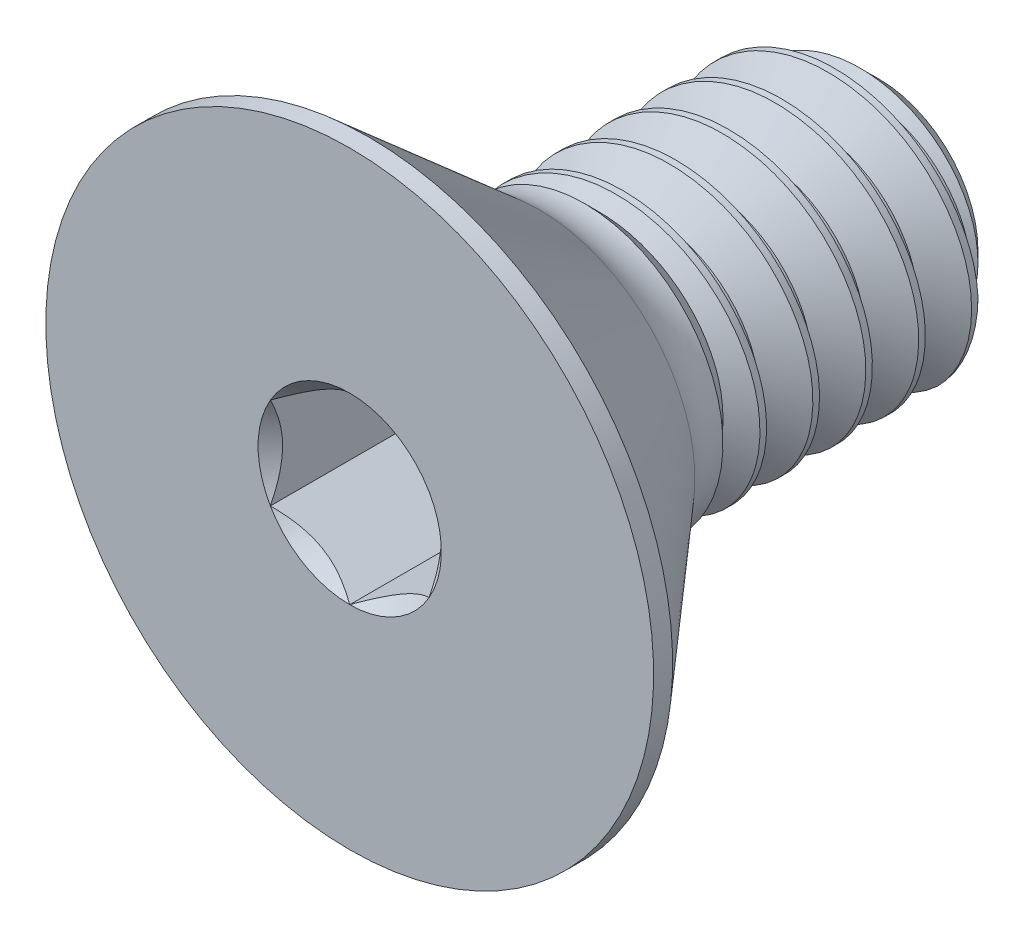
SolidWorks part; units mm, degrees
ref_plane "Front" through (0, 0, 0) normal (0, 0, 1) x (1, 0, 0)
ref_plane "Top" through (0, 0, 0) normal (0, 1, 0) x (1, 0, 0)
ref_plane "Right" through (0, 0, 0) normal (1, 0, 0) x (0, 0, -1)
sketch "Sketch1" plane through (0, 0, 0) normal (1, 0, 0) x (0, 0, -1)
  line L0 (0, 4.5593) -> (0.2845, 4.5593) construction
  line L1 (0.2845, 4.5593) -> (2.8448, 2.3336) construction
  line L2 (0, 2.0828) -> (7.9375, 2.0828)
  line L3 (7.9375, 2.0828) -> (7.9375, 0)
  line L4 (7.9375, 0) -> (0, 0)
  line L5 (0, 0) -> (0, 4.5593) construction
  line L6 (0, 4.5593) -> (0, -4.5593) construction
  line L7 (7.9375, 2.0828) -> (7.9375, -2.0828) construction
  line L8 (0, -4.5593) -> (0.2845, -4.5593) construction
  line L9 (0.2845, -4.5593) -> (2.8448, -2.3336) construction
  line L11 (0, 2.0828) -> (0, 0)
  line L12 (3.5157, 2.0828) -> (3.5157, 0) construction
  arc A1 (2.8448, 2.3336) -> (3.5157, 2.0828) centre (3.5157, 3.1055) ccw construction
  dimension "D1" = 0.2845
  dimension "Head Ht" = 2.8448
  dimension "Head Dia" = 9.1186
  dimension "Dia" = 4.1656
  dimension "Lg" = 7.9375
  dimension "Head Angle" = 82
revolve "Revolve1" add sketch "Sketch1" angle 360 about L4
sketch "Sketch3" plane through (0, 0, -7.9375) normal (0, 0, -1) x (-1, 0, 0)
  circle A0 centre (0, 0) radius 2.0828
curve "Helix/Spiral1" pitch 0.7937 height 7.9375 radius 2.0828 centre (0, 0, -7.9375) axis (0, 0, 1) start towards (0, 1, 0)
sketch "Sketch2" plane through (0, 0, 0) normal (1, 0, 0) x (0, 0, -1)
  line L0 (7.9375, 2.0828) -> (8.632, 2.0828)
  line L1 (8.632, 2.0828) -> (8.3344, 1.5672)
  line L2 (8.3344, 1.5672) -> (8.2352, 1.5672)
  line L3 (8.2352, 1.5672) -> (7.9375, 2.0828)
  line L4 (8.0863, 1.825) -> (8.4832, 1.825) construction
  dimension "D1" = 60
  dimension "D2" = 0.0992
  dimension "D3" = 0.3969
chamfer "Chamfer1" distance 0.5953 angle 45 1 edges at (0, 2.0828, -7.9375)
sweep "Cut-Sweep1" cut profiles "Sketch2" path "Helix/Spiral1"
sketch "Sketch7" plane through (0, 0, 0) normal (1, 0, 0) x (0, 0, -1)
  line L0 (0, 4.5593) -> (0.2845, 4.5593) construction
  line L1 (0.2845, 4.5593) -> (2.8448, 2.3336) construction
  line L2 (0, 4.5593) -> (0.2845, 4.5593)
  line L3 (0.2845, 4.5593) -> (2.8448, 2.3336)
  line L4 (3.5157, 2.0828) -> (3.5157, 0) construction
  line L5 (3.5157, 2.0828) -> (3.5157, 0)
  line L7 (0, 0) -> (0, 4.5593) construction
  line L8 (0, 0) -> (0, 4.5593)
  line L9 (0, 0) -> (3.5157, 0)
  line L10 (5.0152, 0) -> (-5.0152, 0) construction
  arc A0 (2.8448, 2.3336) -> (3.5157, 2.0828) centre (3.5157, 3.1055) ccw construction
  arc A1 (2.8448, 2.3336) -> (3.5157, 2.0828) centre (3.5157, 3.1055) ccw
revolve "Revolve2" add sketch "Sketch7" angle 360 about L9
ref_plane "Plane1" through (0, 0, -3.5157) normal (0, 0, 1) x (1, 0, 0)
sketch "Sketch8" plane through (0, 0, -3.5157) normal (0, 0, 1) x (1, 0, 0)
  circle A0 centre (0, 0) radius 2.0828
extrude "Boss-Extrude1" add sketch "Sketch8" against normal through all draft 45
sketch "Sketch5" plane through (0, 0, 0) normal (0, 0, 1) x (1, 0, 0)
  line L1 (1.1906, -0.6874) -> (1.1906, 0.6874)
  line L2 (1.1906, 0.6874) -> (0, 1.3748)
  line L3 (0, 1.3748) -> (-1.1906, 0.6874)
  line L4 (-1.1906, 0.6874) -> (-1.1906, -0.6874)
  line L5 (-1.1906, -0.6874) -> (0, -1.3748)
  line L6 (0, -1.3748) -> (1.1906, -0.6874)
  circle A0 centre (0, 0) radius 1.1906 construction
  dimension "Hex" = 2.3813
extrude "Cut-Extrude2" cut sketch "Sketch5" against normal blind 1.9914
sketch "Sketch6" plane through (0, 0, 0) normal (0, 0, 1) x (1, 0, 0)
  circle A0 centre (0, 0) radius 1.3748
extrude "Cut-Extrude3" cut sketch "Sketch6" against normal through all draft 45
sketch "Sketch9" [suppressed] plane through (0, 0, -3.9826) normal (0, 0, 1) x (1, 0, 0)
  circle A1 centre (0, 0) radius 2.413
  circle A2 centre (0, 0) radius 2.413
  point P0 (0, 2.413)
  dimension "D1" = 0
extrude "Boss-Extrude2" [suppressed] add sketch "Sketch9" against normal offset from surface (11.8924 mm away) 0.7937 up to face at (0, 1.4875, -7.9375)
sketch "Sketch10" plane through (0, 0, 0) normal (1, 0, 0) x (0, 0, -1)
  line L0 (7.9375, 2.0828) -> (7.9375, -2.0828) construction
  point P0 (6.7469, -2.0828)
  dimension "D1" = 1.1906
equation "\"D3@Helix/Spiral1\" = \"Lg@Sketch1\""
equation "\"D2@Sketch2\" = \"D4@Helix/Spiral1\" * .125"
equation "\"D3@Sketch2\" = \"D4@Helix/Spiral1\" * .5"
equation "\"D1@Chamfer1\" = \"D4@Helix/Spiral1\" * .75"
equation "\"D1@Cut-Extrude2\" = \"Head Ht@Sketch1\" * .7"
equation "\"D1@Sketch1\" = \"Head Ht@Sketch1\" * .1"
equation "\"D1@Sketch10\" = \"D4@Helix/Spiral1\" * 1.5"
